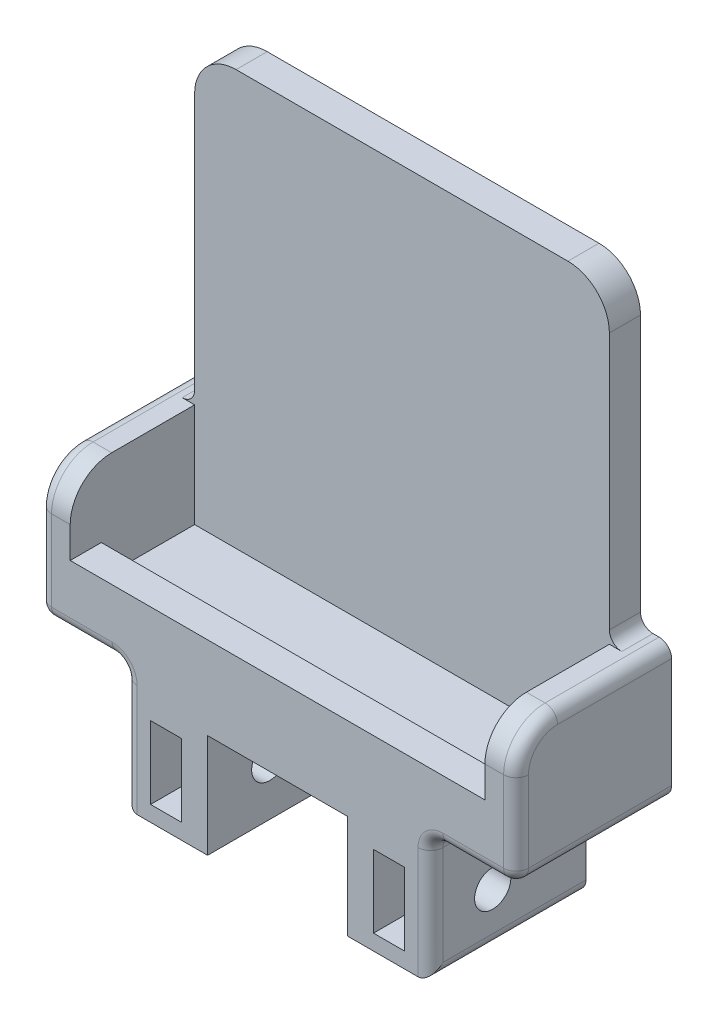
SolidWorks part; units mm, degrees
ref_plane "Front Plane" through (0, 0, 0) normal (0, 0, 1) x (1, 0, 0)
ref_plane "Top Plane" through (0, 0, 0) normal (0, 1, 0) x (1, 0, 0)
ref_plane "Right Plane" through (0, 0, 0) normal (1, 0, 0) x (0, 0, -1)
sketch "Sketch1" plane through (0, 0, 0) normal (0, 0, 1) x (1, 0, 0)
  line L0 (0, 0) -> (0, 5) construction
  line L1 (14.75, 5) -> (-14.75, 5)
  line L2 (-14.75, 5) -> (-14.75, -10)
  line L3 (-14.75, -10) -> (-6.75, -10)
  line L4 (-6.75, -10) -> (-6.75, 0)
  line L5 (-6.75, 0) -> (6.75, 0)
  line L6 (6.75, -10) -> (6.75, 0)
  line L7 (14.75, -10) -> (6.75, -10)
  line L8 (14.75, 5) -> (14.75, -10)
  dimension "D1" = 13.5
  dimension "D2" = 10
  dimension "D3" = 5
  dimension "D4" = 8
extrude "Boss-Extrude1" add sketch "Sketch1" along normal blind 15
sketch "Sketch2" plane through (0, 0, 15) normal (0, 0, 1) x (1, 0, 0)
  line L0 (0, 5) -> (0, 0) construction
  line L1 (14.75, 5) -> (-14.75, 5) construction
  line L2 (-6.75, 0) -> (6.75, 0) construction
  line L3 (6.75, -10) -> (14.75, -10) construction
  line L4 (12.25, -1.5) -> (9.25, -1.5)
  line L5 (12.25, -1.5) -> (12.25, -8.5)
  line L6 (12.25, -8.5) -> (9.25, -8.5)
  line L7 (9.25, -1.5) -> (9.25, -8.5)
  line L8 (12.25, -1.5) -> (9.25, -8.5) construction
  line L9 (12.25, -8.5) -> (9.25, -1.5) construction
  line L10 (6.75, 0) -> (6.75, -10) construction
  line L11 (-12.25, -8.5) -> (-9.25, -1.5) construction
  line L12 (-12.25, -1.5) -> (-9.25, -8.5) construction
  line L13 (-9.25, -1.5) -> (-9.25, -8.5)
  line L14 (-12.25, -8.5) -> (-9.25, -8.5)
  line L15 (-12.25, -1.5) -> (-12.25, -8.5)
  line L16 (-12.25, -1.5) -> (-9.25, -1.5)
  point P6 (10.75, -5)
  point P13 (10.75, -10)
  point P16 (6.75, -5)
  point P21 (-10.75, -5)
  dimension "D1" = 3
  dimension "D2" = 7
extrude "Cut-Extrude1" cut sketch "Sketch2" against normal blind 12
sketch "Sketch3" plane through (14.75, 0, 0) normal (1, 0, 0) x (0, 0, -1)
  line L0 (-15, -10) -> (-15, 5) construction
  line L1 (-3, -8.5) -> (-3, -1.5) construction
  circle A0 centre (-9, -5) radius 1.75
  point P6 (-3, -5)
  dimension "D2" = 3.5
  dimension "D1" = 6
extrude "Cut-Extrude2" cut sketch "Sketch3" against normal through all
sketch "Sketch4" plane through (0, 0, 0) normal (0, 0, 1) x (1, 0, 0)
  line L0 (0, 5) -> (0, 45) construction
  line L1 (14.75, 5) -> (-14.75, 5) construction
  line L2 (-20, 45) -> (20, 45)
  line L3 (20, 45) -> (20, 2)
  line L4 (20, 2) -> (14.75, -3.25)
  line L5 (14.75, -10) -> (14.75, 5) construction
  line L6 (14.75, -3.25) -> (14.75, 5)
  line L7 (14.75, 5) -> (-14.75, 5)
  line L8 (-14.75, -3.25) -> (-14.75, 5)
  line L9 (-20, 2) -> (-14.75, -3.25)
  line L10 (-20, 45) -> (-20, 2)
  dimension "D1" = 45
  dimension "D2" = 40
  dimension "D3" = 40
  dimension "D4" = 3
extrude "Boss-Extrude2" add sketch "Sketch4" along normal blind 3
sketch "Sketch5" plane through (0, 0, 3) normal (0, 0, 1) x (1, 0, 0)
  line L0 (0, 5) -> (0, 3.2351) construction
  line L1 (14.75, 5) -> (-14.75, 5) construction
  line L2 (-14.75, 2) -> (-23, 2)
  line L3 (-23, 2) -> (-23, 15)
  line L4 (-23, 15) -> (-20, 15)
  line L5 (-20, 45) -> (-20, 2) construction
  line L6 (-20, 15) -> (-20, 5)
  line L7 (-20, 5) -> (-14.75, 5)
  line L8 (-14.75, 5) -> (-14.75, 2)
  line L9 (14.75, 5) -> (14.75, 2)
  line L10 (20, 5) -> (14.75, 5)
  line L11 (20, 15) -> (20, 5)
  line L12 (23, 15) -> (20, 15)
  line L13 (23, 2) -> (23, 15)
  line L14 (14.75, 2) -> (23, 2)
  dimension "D1" = 3
  dimension "D2" = 3
  dimension "D3" = 10
extrude "Boss-Extrude4" add sketch "Sketch5" along normal up to surface (12 mm away) and the other way up to surface (3 mm away) up to face at (-10.75, -5, 15) other way up to face at (0, 3.9583, 0)
sketch "Sketch6" plane through (0, 5, 0) normal (0, 1, 0) x (1, 0, 0)
  line L0 (20, -15) -> (20, -3) construction
  line L1 (-20, -15) -> (20, -15)
  line L2 (-20, -15) -> (-20, -12)
  line L3 (-20, -12) -> (20, -12)
  line L4 (20, -15) -> (20, -12)
  line L5 (-20, -3) -> (20, -3) construction
  dimension "D1" = 9
extrude "Boss-Extrude5" add sketch "Sketch6" along normal blind 3
fillet "Fillet1" radius 4 8 edges at (21.5, 15, 15) (-21.5, 15, 15) (-14.75, -3.25, 1.5) (-20, 2, 1.5) (14.75, -3.25, 1.5) (20, 2, 1.5) (20, 45, 1.5) (-20, 45, 1.5)
fillet "Fillet2" radius 1.2 18 edges at (23, 2, 7.5) (-14.75, -10, 7.5) (14.75, -10, 7.5) (-23, 2, 7.5) (14.75, -4, 15) (23, 15, 5.5) (23, 13.8284, 13.8284) (-23, 15, 5.5) (-23, 13.8284, 13.8284) (20, 15, 1.5) (-20, 15, 1.5) (18.875, 2, 15) (23, 6.5, 15) (14.75, 2, 9) (-14.75, 2, 9) (-14.75, -4, 15) (-18.875, 2, 15) (-23, 6.5, 15)
